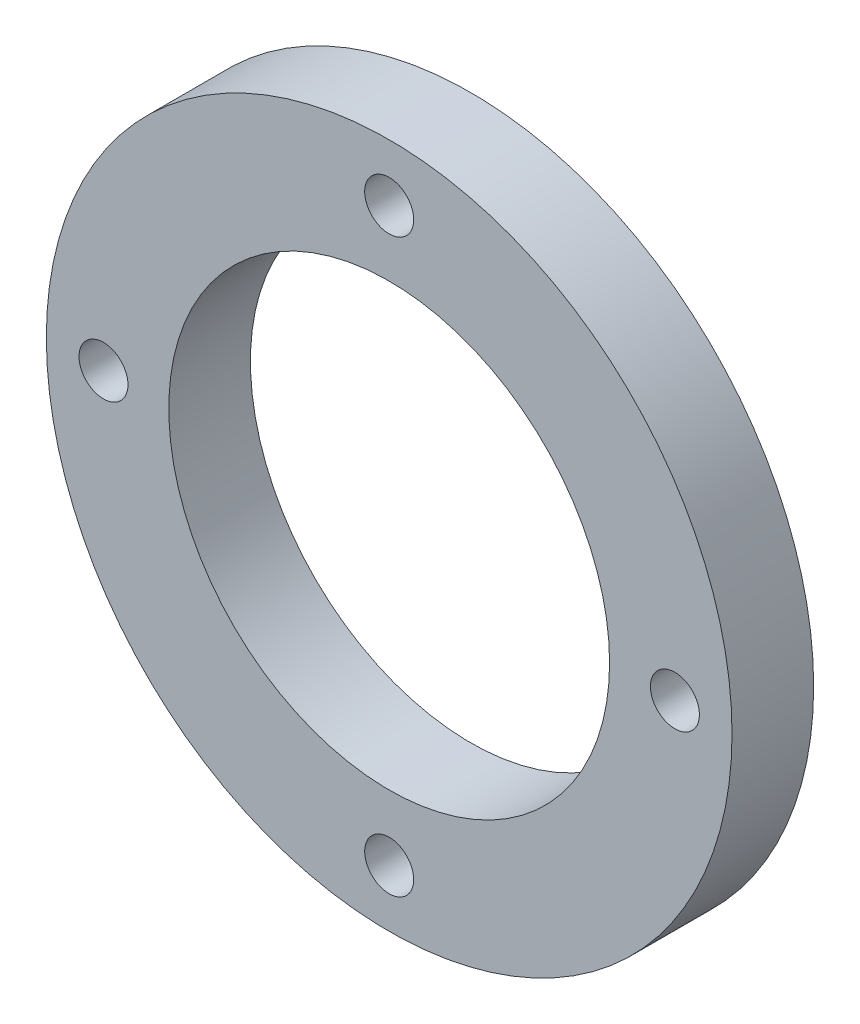
SolidWorks part; units mm, degrees
material "Thornel Mat VMA"
ref_plane "Front Plane" through (0, 0, 0) normal (0, 0, 1) x (1, 0, 0)
ref_plane "Top Plane" through (0, 0, 0) normal (0, 1, 0) x (1, 0, 0)
ref_plane "Right Plane" through (0, 0, 0) normal (1, 0, 0) x (0, 0, -1)
sketch "Sketch1" plane through (0, 0, 0) normal (0, 0, 1) x (1, 0, 0)
  circle A0 centre (49, 5) radius 13 construction
  circle A1 centre (31.5, 5) radius 1.5 construction
  circle A2 centre (49, 22.5) radius 1.5 construction
  circle A3 centre (66.5, 5) radius 1.5 construction
  circle A4 centre (49, -12.5) radius 1.5 construction
  circle A5 centre (49, 5) radius 13
  circle A6 centre (31.5, 5) radius 1.5
  circle A7 centre (49, 22.5) radius 1.5
  circle A8 centre (66.5, 5) radius 1.5
  circle A9 centre (49, -12.5) radius 1.5
  arc A10 (49, -16) -> (49, 26) centre (49, 5) ccw construction
  circle A11 centre (49, 5) radius 21
extrude "Boss-Extrude1" add sketch "Sketch1" along normal blind 5
sketch "Sketch2" plane through (0, 0, 5) normal (0, 0, 1) x (1, 0, 0)
  circle A0 centre (49, 5) radius 13.5
  dimension "D1" = 27
extrude "Cut-Extrude1" cut sketch "Sketch2" against normal blind 10
